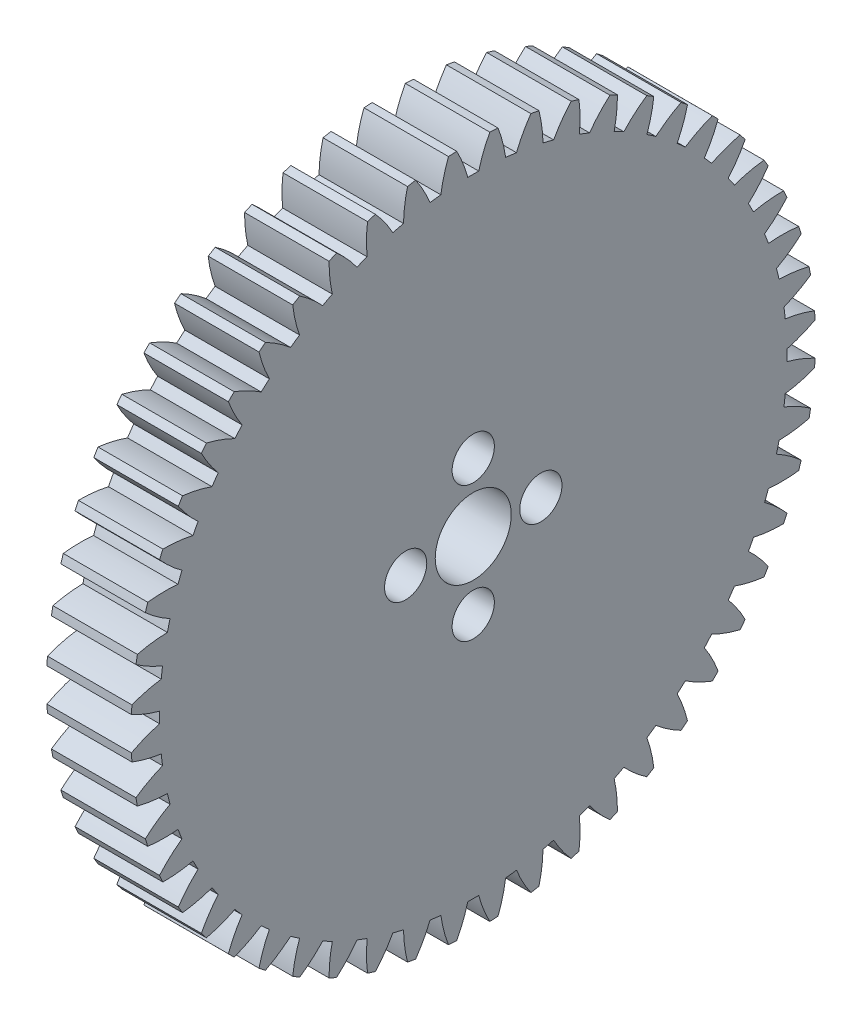
SolidWorks part; units mm, degrees
ref_plane "Plane1" through (0, 0, 0) normal (0, 0, 1) x (1, 0, 0)
ref_plane "Plane2" through (0, 0, 0) normal (0, 1, 0) x (1, 0, 0)
ref_plane "Plane3" through (0, 0, 0) normal (1, 0, 0) x (0, 0, -1)
sketch "HoldingSke" plane through (0, 0, 0) normal (0, 1, 0) x (1, 0, 0)
  line L0 (0, 0) -> (0.4104, -0.5253)
  line L1 (-15, 0) -> (100, 0) construction
  line L2 (0, 0) -> (-2.1039, 2.3779)
  line L3 (0, 0) -> (-11.863, 4.5341)
  line L4 (0, 0) -> (5.3169, 6.8053)
  line L5 (0, 0) -> (-46.8476, -17.4728)
  line L6 (0, 0) -> (-8.2896, -5.593)
  line L7 (-2.1039, 2.3779) -> (8.6586, 51.2059)
  line L8 (-76.2, 54.61) -> (-74.8, 54.61)
  line L9 (-71.009, 38.7566) -> (-53.1078, 45.2721)
  line L10 (-76.2, 71.12) -> (104.1128, 71.12)
  line L11 (0, 0) -> (-10, 0)
  line L12 (-76.2, 101.6) -> (-76.147, 101.6)
  line L13 (24.9733, 27.94) -> (52.9518, 28.4284)
  line L14 (24.9733, 27.94) -> (24.9743, 27.94)
  line L15 (24.9733, 27.94) -> (100.4006, 29.5858)
  line L16 (-63.627, -1.5) -> (-12.827, -1.5)
  circle A0 centre (0, 0) radius 4.5
  circle A1 centre (0, 0) radius 37.124
  circle A2 centre (0, 0) radius 37.5
  circle A3 centre (0, 0) radius 4.5
  dimension "Num_teeth" = 52
  dimension "Pitch_radius" = 180.3128
  dimension "Width" = 10
  dimension "Thickness" = 10
sketch "BasProSke" plane through (0, 0, 0) normal (0, 1, 0) x (1, 0, 0)
  line L0 (-10, 0) -> (60, 0) construction
  line L1 (0, 0) -> (0, 40.5)
  line L2 (0, 0) -> (10, 0)
  line L3 (10, 0) -> (10, 40.5)
  line L4 (10, 40.5) -> (0, 40.5)
  dimension "Thickness" = 10
  dimension "Diameter" = 81
revolve "Base-Revolve" add sketch "BasProSke" angle 360 about L0
sketch "TooCutSke" plane through (0, 0, 0) normal (1, 0, 0) x (0, 0, -1)
  line L1 (0, 0) -> (0, 107) construction
  line L2 (0, 0) -> (-1.2707, 38.9793) construction
  line L3 (0, 0) -> (-4.7077, 77.8275) construction
  line L4 (-1.2707, 38.9793) -> (-2.3538, 38.9138) construction
  arc A0 (0.6474, 37.1184) -> (-0.6474, 37.1184) centre (0, 0) ccw
  arc A1 (1.9744, 40.4773) -> (-1.9744, 40.4773) centre (0, 0) ccw
  circle A2 centre (0, 0) radius 39 construction
  circle A3 centre (0, 0) radius 36.648 construction
  arc A4 (-0.6474, 37.1184) -> (-1.9744, 40.4773) centre (-15.7221, 33.1043) ccw
  arc A5 (1.9744, 40.4773) -> (0.6474, 37.1184) centre (15.7221, 33.1043) ccw
extrude "ToothCut" cut sketch "TooCutSke" along normal through all
fillet "Breaks" [suppressed] radius 0.03 tangent propagation no
fillet "RootFillets" [suppressed] radius 0.376
pattern_circular "TeethCuts" count 52 over 360 about axis through (-10, 0, 0) along (1, 0, 0) of "ToothCut", "RootFillets", "Breaks"
sketch "HubNeaOneSke" plane through (0, 0, 0) normal (-1, 0, 0) x (0, 0, 1)
  circle A0 centre (0, 0) radius 37.124
  dimension "Diameter" = 74.248
extrude "HubNearOne" [suppressed] add sketch "HubNeaOneSke" along normal blind 40.0001
sketch "HubNeaBotSke" plane through (0, 0, 0) normal (-1, 0, 0) x (0, 0, 1)
  circle A0 centre (0, 0) radius 37.124
  dimension "Diameter" = 74.248
extrude "HubNearBoth" [suppressed] add sketch "HubNeaBotSke" along normal blind 20
ref_plane "FarPln" through (10, 0, 0) normal (1, 0, 0) x (0, 0, -1)
sketch "HubFarSke" plane through (10, 0, 0) normal (1, 0, 0) x (0, 0, -1)
  circle A0 centre (0, 0) radius 37.124
  dimension "Diameter" = 74.248
extrude "HubFar" [suppressed] add sketch "HubFarSke" along normal blind 20
sketch "BorSke" plane through (0, 0, 0) normal (1, 0, 0) x (0, 0, -1)
  circle A0 centre (0, 0) radius 4.5
  dimension "Diameter" = 9
extrude "Bore" cut sketch "BorSke" along normal mid plane 100.0001
sketch "KeySke" plane through (0, 0, 0) normal (1, 0, 0) x (0, 0, -1)
  line L0 (-1.5, 0) -> (-1.5, 5.9)
  line L1 (-1.5, 5.9) -> (1.5, 5.9)
  line L2 (1.5, 5.9) -> (1.5, 0)
  line L3 (0, 0) -> (0, 34) construction
  line L4 (-1.5, 0) -> (1.5, 0)
  dimension "Width" = 3
extrude "Keyway" [suppressed] cut sketch "KeySke" along normal mid plane 100.0001
pattern_circular "Keyway2" [suppressed] count 2 every 90 about axis through (-10, 0, 0) along (1, 0, 0) reverse direction yes
sketch "Esquisse2" plane through (0, 0, 0) normal (-1, 0, 0) x (0, 0, 1)
  circle A1 centre (8, 0) radius 1.125
  circle A4 centre (0, 0) radius 4.5 construction
  circle A5 centre (0, 0) radius 4.5 construction
  circle A6 centre (0, -8) radius 1.125
  circle A7 centre (-8, 0) radius 1.125
  circle A8 centre (0, 8) radius 1.125
  point P14 (0, 0)
  dimension "D1" = 2.25
  dimension "D3" = 4
  dimension "D2" = 8
extrude "Enlèv. mat.-Extru.1" cut sketch "Esquisse2" against normal up to next
sketch "Esquisse3" plane through (0, 0, 0) normal (-1, 0, 0) x (0, 0, 1)
  circle A0 centre (0, 0) radius 15
  circle A1 centre (0, -8) radius 1.125 construction
  circle A2 centre (8, 0) radius 1.125 construction
  circle A3 centre (0, 8) radius 1.125 construction
  circle A4 centre (-8, 0) radius 1.125 construction
  circle A5 centre (0, 0) radius 4.5 construction
  circle A6 centre (0, -8) radius 1.125
  circle A7 centre (8, 0) radius 1.125
  circle A8 centre (0, 8) radius 1.125
  circle A9 centre (-8, 0) radius 1.125
  circle A10 centre (0, 0) radius 4.5
  dimension "D1" = 30
extrude "Boss.-Extru.1" add sketch "Esquisse3" along normal blind 13
sketch "Esquisse4" plane through (10, 0, 0) normal (1, 0, 0) x (0, 0, -1)
  circle A0 centre (0, 8) radius 2.5
  circle A1 centre (8, 0) radius 2.5
  circle A2 centre (0, -8) radius 2.5
  circle A3 centre (-8, 0) radius 2.5
  dimension "D1" = 5
extrude "Enlèv. mat.-Extru.2" cut sketch "Esquisse4" against normal offset from surface (14 mm away) 9 up to face at (-13, 0, -6.875)
sketch "Esquisse6" plane through (0, 0, 0) normal (-1, 0, 0) x (0, 0, 1)
  circle A0 centre (0, 0) radius 35
  circle A1 centre (0, 0) radius 15 construction
  circle A2 centre (0, 0) radius 15
  dimension "D1" = 70
extrude "Enlèv. mat.-Extru.4" cut sketch "Esquisse6" against normal blind 6
sketch "Esquisse5" plane through (-13, 0, 0) normal (-1, 0, 0) x (0, 0, 1)
  circle A0 centre (0, 0) radius 10.5
  circle A1 centre (0, 0) radius 15 construction
  circle A2 centre (0, 0) radius 15
  dimension "D1" = 21
extrude "Enlèv. mat.-Extru.3" cut sketch "Esquisse5" against normal blind 5
chamfer "Chanfrein1" distance 4.5 angle 45 1 edges at (-8, 0, 15)
sketch "Esquisse7" plane through (6, 0, 0) normal (-1, 0, 0) x (0, 0, 1)
  circle A0 centre (0, 0) radius 4.5 construction
  circle A1 centre (0, 0) radius 4.5 construction
  text T0 "<b>52</b>"
  dimension "D1" = 30
  dimension "D2" = 3
extrude "Tooth count" cut sketch "Esquisse7" against normal blind 1.5
equation "' \"Module@HoldingSke\" = 6.35"
equation "' \"Num_teeth@HoldingSke\" = 12"
equation "' \"Ap@HoldingSke\" =  20"
equation "' \"Ap@HoldingSke\" = 20"
equation "' \"Width@HoldingSke\" = 0.5 * 25.4"
equation "' \"Hub_dia@HoldingSke\"= 1 * 25.4"
equation "' \"Hub_dia@HoldingSke\" = 1 * 25.4"
equation "' \"Overall_len@HoldingSke\" = 1.0 * 25.4"
equation "' \"Bore@HoldingSke\" = 0.75 * 25.4"
equation "' \"T_dim@HoldingSke\" = 0.1 * 25.4"
equation "' \"Width@KeySke\" = 0.25 * 25.4"
equation "' \"Show_teeth@HoldingSke\" = 13"
equation "' \"Backlash@HoldingSke\" = 0.009 * 25.4"
equation "' \"Addendum_fac@HoldingSke\" = 1.0"
equation "' \"Dedendum_fac@HoldingSke\" = 1.25"
equation "' \"Dedendum_add@HoldingSke\" = 0.00005 * 25.4"
equation "' \"Clearance_fac@HoldingSke\" = 0.25"
equation "\"Pitch@HoldingSke\" = 1 / \"Module@HoldingSke\""
equation "\"Overcut_dia@TooCutSke\" = (\"Num_teeth@HoldingSke\" + 2 * \"Addendum_fac@HoldingSke\") / \"Pitch@HoldingSke\" + 0.002 * 25.4"
equation "\"Pitch_dia@TooCutSke\" = \"Num_teeth@HoldingSke\" / \"Pitch@HoldingSke\""
equation "\"Base_dia@TooCutSke\" = \"Num_teeth@HoldingSke\" / \"Pitch@HoldingSke\" * cos((\"Ap@HoldingSke\"  * 3.14159265 / 180))"
equation "\"Root_dia@TooCutSke\" = (\"Num_teeth@HoldingSke\" + 2) / \"Pitch@HoldingSke\" - 2 * (\"Addendum_fac@HoldingSke\" + \"Dedendum_fac@HoldingSke\") / \"Pitch@HoldingSke\" - \"Dedendum_add@HoldingSke\" * 2"
equation "\"Half_ang@TooCutSke\" = 180 / \"Num_teeth@HoldingSke\""
equation "\"Half_CT@TooCutSke\" = \"Num_teeth@HoldingSke\" / \"Pitch@HoldingSke\" * sin((3.14159265 / 2 / \"Num_teeth@HoldingSke\")) / 2 - 7 * \"Backlash@HoldingSke\" / 4"
equation "\"Flank_rad@TooCutSke\" = \"Num_teeth@HoldingSke\" / \"Pitch@HoldingSke\" / 5"
equation "\"Radius@RootFillets\" = \"Clearance_fac@HoldingSke\" / \"Pitch@HoldingSke\" + \"Dedendum_add@HoldingSke\""
equation "\"Break_rad@Breaks\" = 0.02 / \"Pitch@HoldingSke\""
equation "\"Thickness@HoldingSke\" = \"Width@HoldingSke\""
equation "\"OAL@HoldingSke\" = \"Thickness@HoldingSke\""
equation "\"MHD@HoldingSke\" = (\"Num_teeth@HoldingSke\" + 2) / \"Pitch@HoldingSke\" - 2 * (\"Addendum_fac@HoldingSke\" + \"Dedendum_fac@HoldingSke\")  / \"Pitch@HoldingSke\" - \"Dedendum_add@HoldingSke\" * 2"
equation "\"MBD@HoldingSke\" = (\"Num_teeth@HoldingSke\" + 2) / \"Pitch@HoldingSke\" - 2 * (\"Addendum_fac@HoldingSke\" + \"Dedendum_fac@HoldingSke\")  / \"Pitch@HoldingSke\" - \"Dedendum_add@HoldingSke\" * 2 - 0.002 * 25.4"
equation "\"MHD@HoldingSke\" = ((sgn( \"MHD@HoldingSke\" - \"Hub_dia@HoldingSke\" )-1)*( \"MHD@HoldingSke\" - \"Hub_dia@HoldingSke\" ))/-2+ \"Hub_dia@HoldingSke\""
equation "\"MBD@HoldingSke\" = ((sgn( \"MBD@HoldingSke\" - \"Bore@HoldingSke\" )-1)*( \"MBD@HoldingSke\" - \"Bore@HoldingSke\" ))/-2+ \"Bore@HoldingSke\""
equation "\"OAL@HoldingSke\" = ((sgn( \"OAL@HoldingSke\" - \"Overall_len@HoldingSke\" )+1)*( \"OAL@HoldingSke\" - \"Overall_len@HoldingSke\" ))/2 + \"Overall_len@HoldingSke\" + 0.000002 * 25.4"
equation "\"Num_teeth@TeethCuts\" = int( \"Show_teeth@HoldingSke\" ) + 1"
equation "\"Num_teeth@TeethCuts\" = ((sgn( \"Num_teeth@TeethCuts\" - \"Num_teeth@HoldingSke\" )-1)*( \"Num_teeth@TeethCuts\" - \"Num_teeth@HoldingSke\" ))/-2+ \"Num_teeth@HoldingSke\""
equation "\"Num_teeth@TeethCuts\" = ((sgn( \"Num_teeth@TeethCuts\" - 2.0)+1)*( \"Num_teeth@TeethCuts\" - 2.0))/2 +2.0"
equation "\"Angle@TeethCuts\" = 360.0 / \"Num_teeth@HoldingSke\""
equation "\"Diameter@BasProSke\" = (\"Num_teeth@HoldingSke\" + 2 * \"Addendum_fac@HoldingSke\") / \"Pitch@HoldingSke\""
equation "\"Thickness@BasProSke\"  = \"Thickness@HoldingSke\""
equation "' \"Fillet_rad@BasProSke\" =  \"Thickness@HoldingSke\" * 0.05"
equation "' \"Fillet_rad@BasProSke\" = \"Thickness@HoldingSke\" * 0.05"
equation "\"MHD@HoldingSke\" = ((sgn( \"MHD@HoldingSke\" - \"Root_dia@TooCutSke\" )-1)*( \"MHD@HoldingSke\" - \"Root_dia@TooCutSke\" ))/-2+ \"Root_dia@TooCutSke\""
equation "\"Diameter@HubNeaOneSke\" = \"MHD@HoldingSke\""
equation "\"Length@HubNearOne\" = \"OAL@HoldingSke\" - \"Thickness@BasProSke\""
equation "\"Diameter@HubNeaBotSke\" = \"MHD@HoldingSke\""
equation "\"Length@HubNearBoth\" = ( \"OAL@HoldingSke\" - \"Thickness@BasProSke\" ) / 2.0"
equation "\"Thickness@FarPln\" = \"Thickness@BasProSke\""
equation "\"Diameter@HubFarSke\" = \"MHD@HoldingSke\""
equation "\"Length@HubFar\" = ( \"OAL@HoldingSke\" - \"Thickness@BasProSke\" ) / 2.0"
equation "\"Diameter@BorSke\" = \"MBD@HoldingSke\""
equation "\"D1@Bore\" = \"OAL@HoldingSke\" * 2.0"
equation "\"D1@Keyway\" = \"OAL@HoldingSke\" * 2.0"
equation "\"Offset@KeySke\" = \"T_dim@HoldingSke\" + \"MBD@HoldingSke\" / 2.0"
